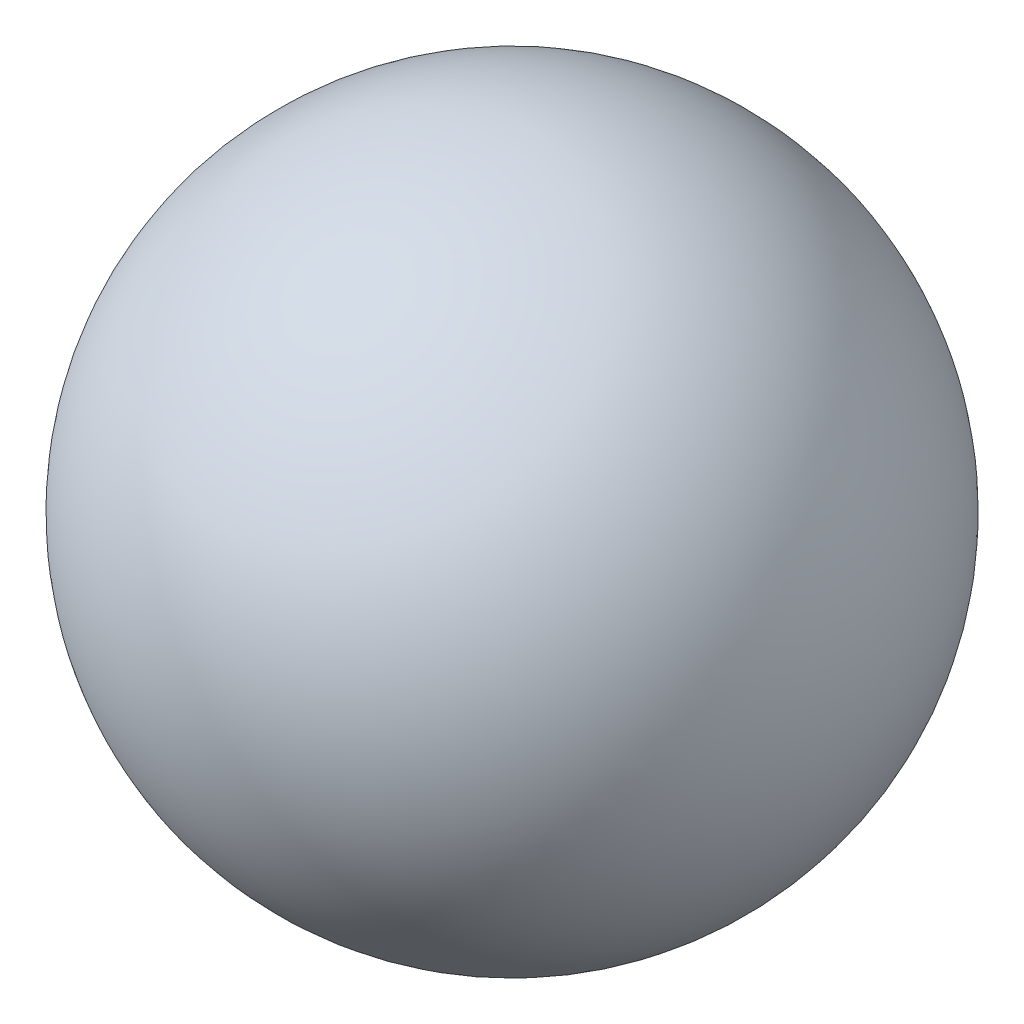
SolidWorks part; units mm, degrees
ref_plane "Front Plane" through (0, 0, 0) normal (0, 0, 1) x (1, 0, 0)
ref_plane "Top Plane" through (0, 0, 0) normal (0, 1, 0) x (1, 0, 0)
ref_plane "Right Plane" through (0, 0, 0) normal (1, 0, 0) x (0, 0, -1)
sketch "Sketch3" plane through (0, 0, 0) normal (0, 1, 0) x (1, 0, 0)
  line L0 (0, -2.3813) -> (0, 2.3813)
  arc A0 (0, 2.3813) -> (0, -2.3813) centre (0, 0) cw
  dimension "D2" = 2.3813
ref_axis "Axis3" through (0, 0, -2.3813) along (0, 0, 1)
revolve "Revolve4" add sketch "Sketch3" angle 360 about L0
